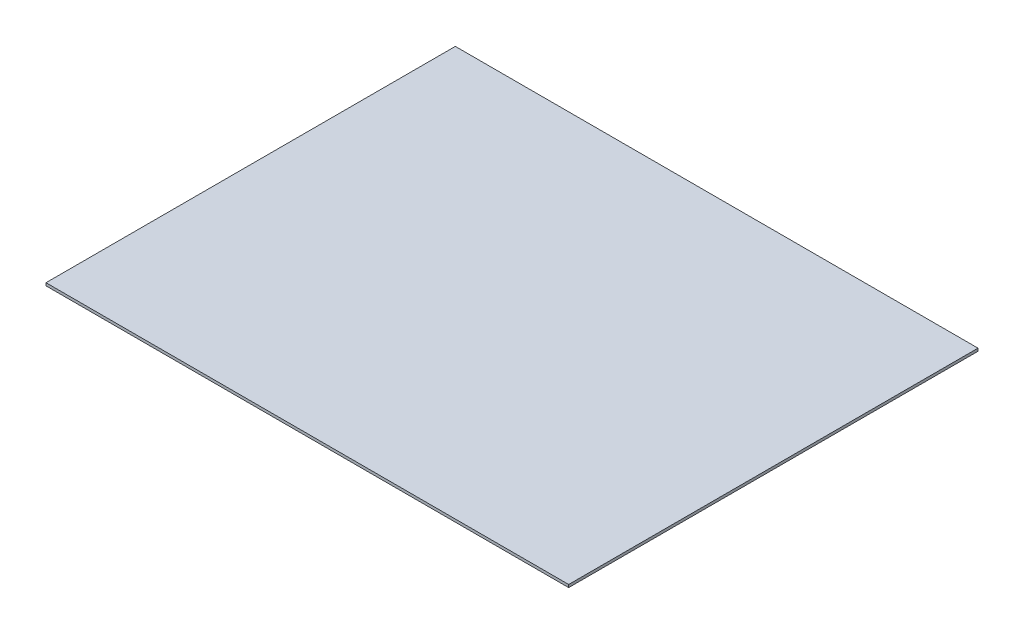
SolidWorks part; units mm, degrees
ref_plane "Front Plane" through (0, 0, 0) normal (0, 0, 1) x (1, 0, 0)
ref_plane "Top Plane" through (0, 0, 0) normal (0, 1, 0) x (1, 0, 0)
ref_plane "Right Plane" through (0, 0, 0) normal (1, 0, 0) x (0, 0, -1)
sketch "Sketch1" plane through (0, 0, 0) normal (0, 1, 0) x (1, 0, 0)
  line L1 (-124.5, 97.5) -> (124.5, 97.5)
  line L2 (-124.5, 97.5) -> (-124.5, -97.5)
  line L3 (-124.5, -97.5) -> (124.5, -97.5)
  line L4 (124.5, 97.5) -> (124.5, -97.5)
  line L5 (-124.5, 97.5) -> (124.5, -97.5) construction
  line L6 (-124.5, -97.5) -> (124.5, 97.5) construction
  point P0 (0, 0)
  dimension "D1" = 249
  dimension "D2" = 195
extrude "Boss-Extrude1" add sketch "Sketch1" along normal blind 1.3
